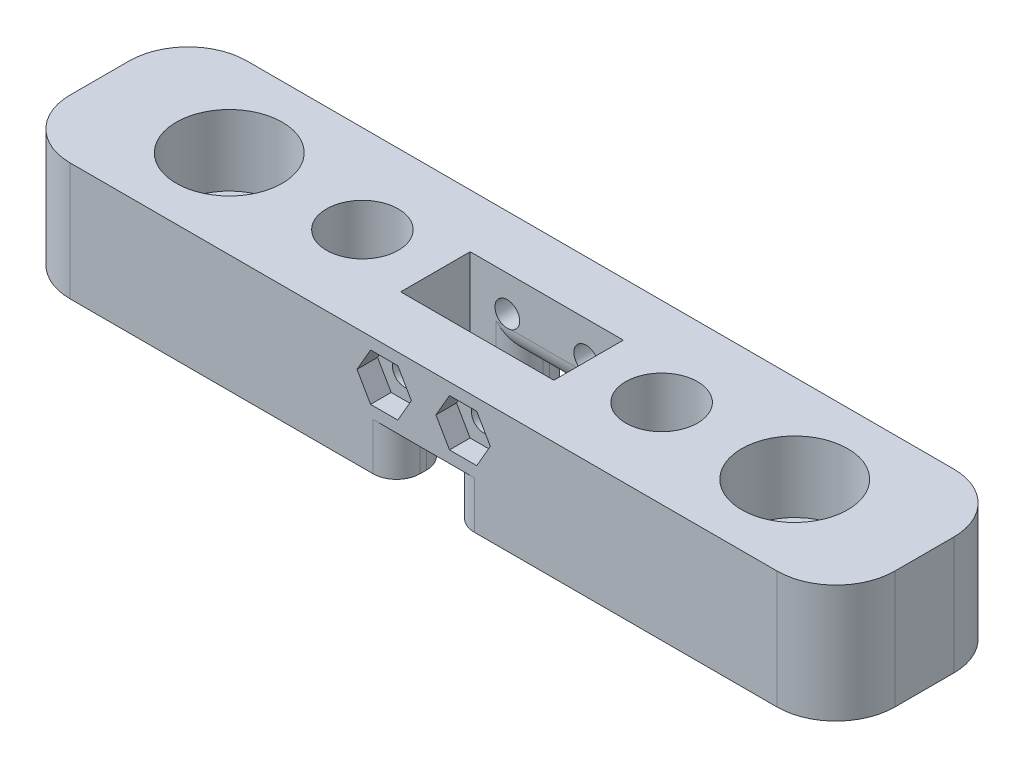
SolidWorks part; units mm, degrees
ref_plane "Front Plane" through (0, 0, 0) normal (0, 0, 1) x (1, 0, 0)
ref_plane "Top Plane" through (0, 0, 0) normal (0, 1, 0) x (1, 0, 0)
ref_plane "Right Plane" through (0, 0, 0) normal (1, 0, 0) x (0, 0, -1)
sketch "Sketch1" plane through (0, 0, 0) normal (0, 0, 1) x (1, 0, 0)
  line L1 (0, 0) -> (40, 0)
  line L2 (0, 0) -> (0, 10)
  line L3 (0, 10) -> (40, 10)
  line L4 (40, 0) -> (40, 10)
  dimension "D1" = 40
  dimension "D2" = 10
extrude "SwitchCase" add sketch "Sketch1" along normal blind 15
sketch "Sketch2" plane through (0, 10, 0) normal (0, 1, 0) x (1, 0, 0)
  line L1 (13.5, -4.55) -> (26.5, -4.55)
  line L2 (13.5, -4.55) -> (13.5, -10.45)
  line L3 (13.5, -10.45) -> (26.5, -10.45)
  line L4 (26.5, -4.55) -> (26.5, -10.45)
  line L5 (40, 0) -> (0, 0) construction
  point P4 (20, 0)
  point P5 (20, -4.55)
  point P9 (13.5, -7.5)
  dimension "D1" = 5.9
  dimension "D2" = 13
  dimension "D4" = 7.5
extrude "SwitchCavity" cut sketch "Sketch2" against normal through all
sketch "Sketch3" plane through (0, 0, 4.55) normal (0, 0, 1) x (1, 0, 0)
  line L0 (13.5, 0) -> (13.5, 10) construction
  line L1 (26.5, 0) -> (26.5, 10) construction
  line L3 (40, 10) -> (0, 10) construction
  line L4 (26.5, 10) -> (13.5, 10) construction
  circle A0 centre (16.65, 7) radius 1.05
  circle A1 centre (23.35, 7) radius 1.05
  dimension "D1" = 2.1
  dimension "D2" = 3.15
  dimension "D3" = 3.15
  dimension "D4" = 3
  dimension "D5" = 3
extrude "SwitchM2Holes" cut sketch "Sketch3" against normal through all both and the other way through all
sketch "Sketch14" plane through (0, 0, 0) normal (0, 0, -1) x (-1, 0, 0)
  line L0 (-20, 10) -> (-20, -0.8547) construction
  line L3 (-40, 10) -> (0, 10) construction
  circle A0 centre (-23.35, 7) radius 2
  circle A2 centre (-16.65, 7) radius 2
  dimension "D1" = 4
extrude "M2Head" cut sketch "Sketch14" against normal blind 1.5
sketch "Sketch5" plane through (0, 0, 15) normal (0, 0, 1) x (1, 0, 0)
  line L1 (18.9594, 7) -> (17.8047, 9)
  line L2 (17.8047, 9) -> (15.4953, 9)
  line L3 (15.4953, 9) -> (14.3406, 7)
  line L4 (14.3406, 7) -> (15.4953, 5)
  line L5 (15.4953, 5) -> (17.8047, 5)
  line L6 (17.8047, 5) -> (18.9594, 7)
  line L8 (25.6594, 7) -> (24.5047, 9)
  line L9 (24.5047, 9) -> (22.1953, 9)
  line L10 (22.1953, 9) -> (21.0406, 7)
  line L11 (21.0406, 7) -> (22.1953, 5)
  line L12 (22.1953, 5) -> (24.5047, 5)
  line L13 (24.5047, 5) -> (25.6594, 7)
  circle A0 centre (16.65, 7) radius 2 construction
  circle A1 centre (23.35, 7) radius 2 construction
  dimension "D1" = 4
  dimension "D2" = 2
extrude "M2NutInserts" cut sketch "Sketch5" against normal blind 1.75 and the other way through all
sketch "Sketch7" plane through (0, 0, 15) normal (0, 0, 1) x (1, 0, 0)
  line L0 (0, 10) -> (-15, 10)
  line L2 (0, 0) -> (0, 10)
  line L3 (40, 10) -> (55, 10)
  line L5 (40, 0) -> (40, 10)
  line L6 (0, 0) -> (-15, 0)
  line L7 (-15, 0) -> (-15, 10)
  line L8 (40, 0) -> (55, 0)
  line L9 (55, 0) -> (55, 10)
  point P5 (0, 0)
  point P8 (0, 0)
  dimension "D1" = 15
  dimension "D2" = 10
extrude "Wings" add sketch "Sketch7" against normal up to surface (15 mm away) up to face at (21.35, 7, 0)
sketch "Sketch9" plane through (0, 0, 0) normal (0, -1, 0) x (1, 0, 0)
  line L1 (37.2322, 7.5) -> (34.9661, 11.425)
  line L2 (34.9661, 11.425) -> (30.4339, 11.425)
  line L3 (30.4339, 11.425) -> (28.1678, 7.5)
  line L4 (28.1678, 7.5) -> (30.4339, 3.575)
  line L5 (30.4339, 3.575) -> (34.9661, 3.575)
  line L6 (34.9661, 3.575) -> (37.2322, 7.5)
  line L9 (26.5, 10.45) -> (26.5, 4.55) construction
  line L10 (20, 10.45) -> (20, 4.55) construction
  line L11 (13.5, 10.45) -> (26.5, 10.45) construction
  line L12 (26.5, 4.55) -> (13.5, 4.55) construction
  line L19 (5.0339, 3.575) -> (2.7678, 7.5)
  line L20 (9.5661, 3.575) -> (5.0339, 3.575)
  line L21 (11.8322, 7.5) -> (9.5661, 3.575)
  line L22 (9.5661, 11.425) -> (11.8322, 7.5)
  line L23 (5.0339, 11.425) -> (9.5661, 11.425)
  line L24 (2.7678, 7.5) -> (5.0339, 11.425)
  circle A0 centre (32.7, 7.5) radius 3.925 construction
  point P26 (26.5, 7.5)
  dimension "D2" = 3.925
  dimension "D1" = 7.85
  dimension "D3" = 12.7
extrude "M5Nuts" cut sketch "Sketch9" against normal blind 4
sketch "Sketch10" plane through (0, 0, 0) normal (0, -1, 0) x (1, 0, 0)
  line L1 (9.5661, 11.425) -> (5.0339, 11.425) construction
  line L2 (20, 10.45) -> (20, 4.55) construction
  line L3 (13.5, 10.45) -> (26.5, 10.45) construction
  line L4 (26.5, 4.55) -> (13.5, 4.55) construction
  circle A0 centre (7.3, 7.5) radius 3.05
  circle A3 centre (32.7, 7.5) radius 3.05
  point P7 (7.3, 11.425)
  dimension "D1" = 6.1
extrude "M6Hole" cut sketch "Sketch10" against normal through all
sketch "Sketch11" plane through (0, 0, 4.55) normal (0, 0, 1) x (1, 0, 0)
  line L1 (22.3, 4) -> (17.7, 4)
  line L2 (22.3, 4) -> (22.3, 0)
  line L3 (22.3, 0) -> (17.7, 0)
  line L4 (17.7, 4) -> (17.7, 0)
  line L6 (26.5, 0) -> (13.5, 0) construction
  circle A1 centre (16.65, 7) radius 1.05 construction
  point P4 (20, 0)
  point P5 (20, 0)
  dimension "D1" = 4
extrude "WireChannel" cut sketch "Sketch11" against normal through all both and the other way through all
fillet "ChannelFillet" radius 2 10 edges at (17.7, 2, 4.55) (17.7, 2, 0) (17.7, 2, 10.45) (17.7, 2, 15) (20, 4, 10.45) (20, 4, 4.55) (22.3, 2, 0) (22.3, 2, 4.55) (22.3, 2, 10.45) (22.3, 2, 15)
sketch "Sketch12" plane through (0, 10, 0) normal (0, 1, 0) x (1, 0, 0)
  line L0 (26.5, -4.55) -> (13.5, -4.55) construction
  line L1 (26.5, -10.45) -> (26.5, -4.55) construction
  line L2 (20, -4.55) -> (20, -10.45) construction
  line L3 (13.5, -10.45) -> (26.5, -10.45) construction
  circle A0 centre (44, -7.5) radius 4.5
  circle A1 centre (-4, -7.5) radius 4.5
  point P4 (20, -4.55)
  point P7 (26.5, -7.5)
  dimension "D1" = 9
  dimension "D2" = 24
extrude "M5Head" cut sketch "Sketch12" against normal blind 6 and the other way through all
sketch "Sketch13" plane through (0, 10, 0) normal (0, 1, 0) x (1, 0, 0)
  line L0 (20, -4.55) -> (20, -10.45) construction
  line L1 (26.5, -4.55) -> (13.5, -4.55) construction
  line L2 (13.5, -10.45) -> (26.5, -10.45) construction
  circle A0 centre (44, -7.5) radius 2.75
  circle A1 centre (-4, -7.5) radius 2.75
  dimension "D1" = 5.5
extrude "M5Thread" cut sketch "Sketch13" against normal through all
fillet "EndFillet" radius 5 4 edges at (-15, 5, 15) (-15, 5, 0) (55, 5, 15) (55, 5, 0)
